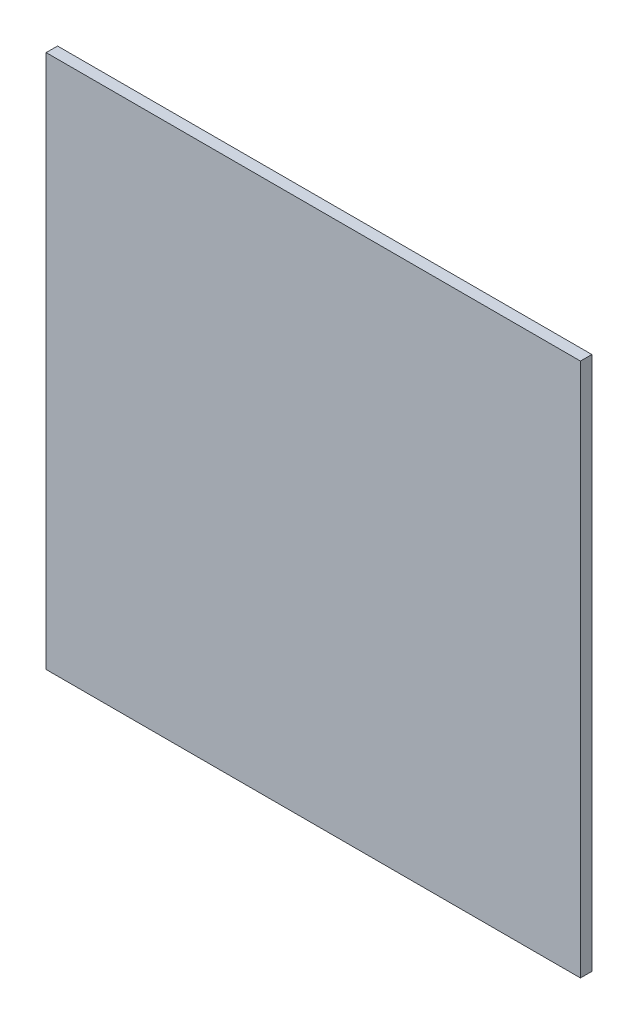
SolidWorks part; units mm, degrees
ref_plane "Front Plane" through (0, 0, 0) normal (0, 0, 1) x (1, 0, 0)
ref_plane "Top Plane" through (0, 0, 0) normal (0, 1, 0) x (1, 0, 0)
ref_plane "Right Plane" through (0, 0, 0) normal (1, 0, 0) x (0, 0, -1)
sketch "Sketch1" plane through (0, 0, 0) normal (0, 0, 1) x (1, 0, 0)
  line L1 (-37.5, -37.5) -> (37.5, -37.5)
  line L2 (-37.5, -37.5) -> (-37.5, 37.5)
  line L3 (-37.5, 37.5) -> (37.5, 37.5)
  line L4 (37.5, -37.5) -> (37.5, 37.5)
  line L5 (-37.5, -37.5) -> (37.5, 37.5) construction
  line L6 (-37.5, 37.5) -> (37.5, -37.5) construction
  point P0 (0, 0)
  dimension "D1" = 75
  dimension "D2" = 75
extrude "Boss-Extrude1" add sketch "Sketch1" along normal blind 1.6
